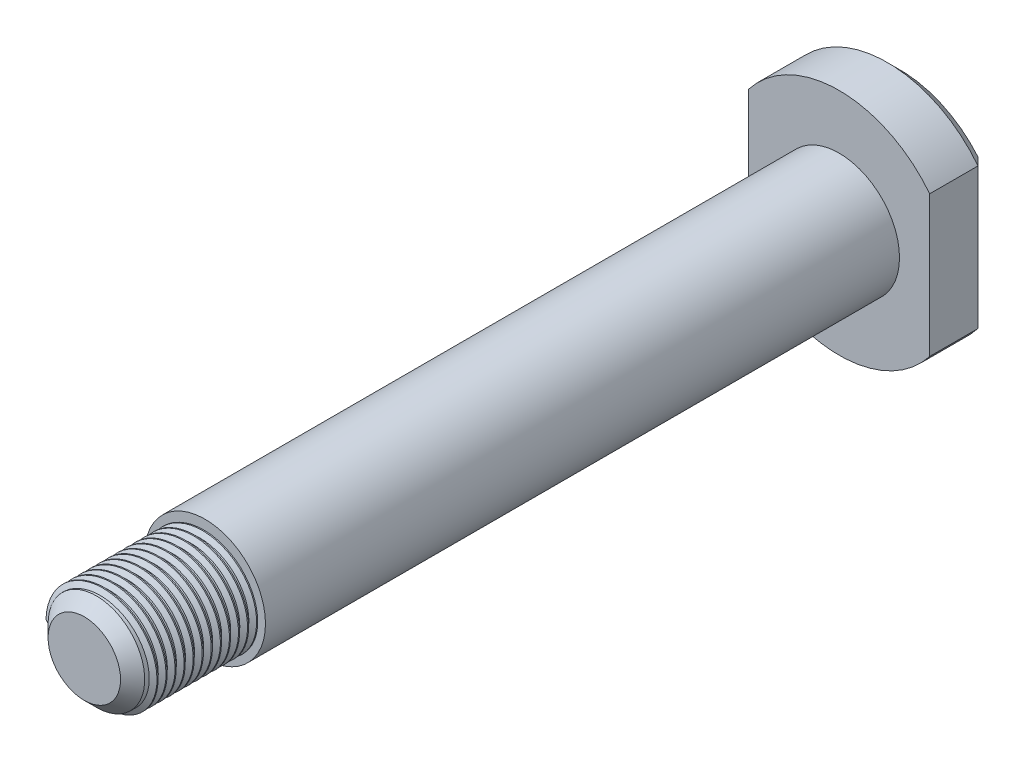
SolidWorks part; units mm, degrees
ref_plane "Front Plane" through (0, 0, 0) normal (0, 0, 1) x (1, 0, 0)
ref_plane "Top Plane" through (0, 0, 0) normal (0, 1, 0) x (1, 0, 0)
ref_plane "Right Plane" through (0, 0, 0) normal (1, 0, 0) x (0, 0, -1)
sketch "Sketch1" plane through (0, 0, 0) normal (0, 0, 1) x (1, 0, 0)
  line L3 (-15, 11.6619) -> (-15, -11.6619)
  line L4 (15, 11.6619) -> (15, -11.6619)
  arc A0 (-15, -11.6619) -> (15, -11.6619) centre (0, 0) ccw
  arc A1 (15, 11.6619) -> (-15, 11.6619) centre (0, 0) ccw
  point P1 (-5.4257, 0)
extrude "Boss-Extrude1" add sketch "Sketch1" along normal blind 10
chamfer "Chamfer1" distance 2 angle 45 4 edges at (-15, 0, 0) (0, -19, 0) (15, 0, 0) (0, 19, 0)
sketch "Sketch2" plane through (0, 0, 10) normal (0, 0, 1) x (1, 0, 0)
  circle A0 centre (0, 0) radius 10
extrude "Boss-Extrude2" add sketch "Sketch2" along normal blind 105
sketch "Sketch3" plane through (0, 0, 115) normal (0, 0, 1) x (1, 0, 0)
  circle A0 centre (0, 0) radius 8
extrude "Boss-Extrude3" add sketch "Sketch3" along normal blind 20
chamfer "Chamfer2" distance 2 angle 45 1 edges at (8, 0, 135)
thread "Thread1" pitch 1.5 method extrude profile "Thread Profile1" start angle 0, offset 0, length 0, pitch 1.5, diameter 16
ref_plane "Plane1" through (-8, 0, 133) normal (0, -1, 0) x (-1, 0, 0)
sketch "Thread Profile1" plane through (-8, 0, 133) normal (0, -1, 0) x (-1, 0, 0)
  line L0 (0, 0) -> (0, 1.5) construction
  line L1 (0, 0) -> (0.8119, 0.4687)
  line L2 (0.8119, 0.4687) -> (0.8119, 0.6562)
  line L3 (0.8119, 0.6562) -> (0, 1.125)
  line L4 (0.8119, 0.5625) -> (0, 0.5625) construction
  line L11 (0, 0) -> (0, 1.125)
  point P2 (0, 0)
  dimension "Pitch" = 1.5
  dimension "Profile_Angle" = 60
  dimension "Profile_Land" = 0.1875
  dimension "Profile_Height" = 0.8119
